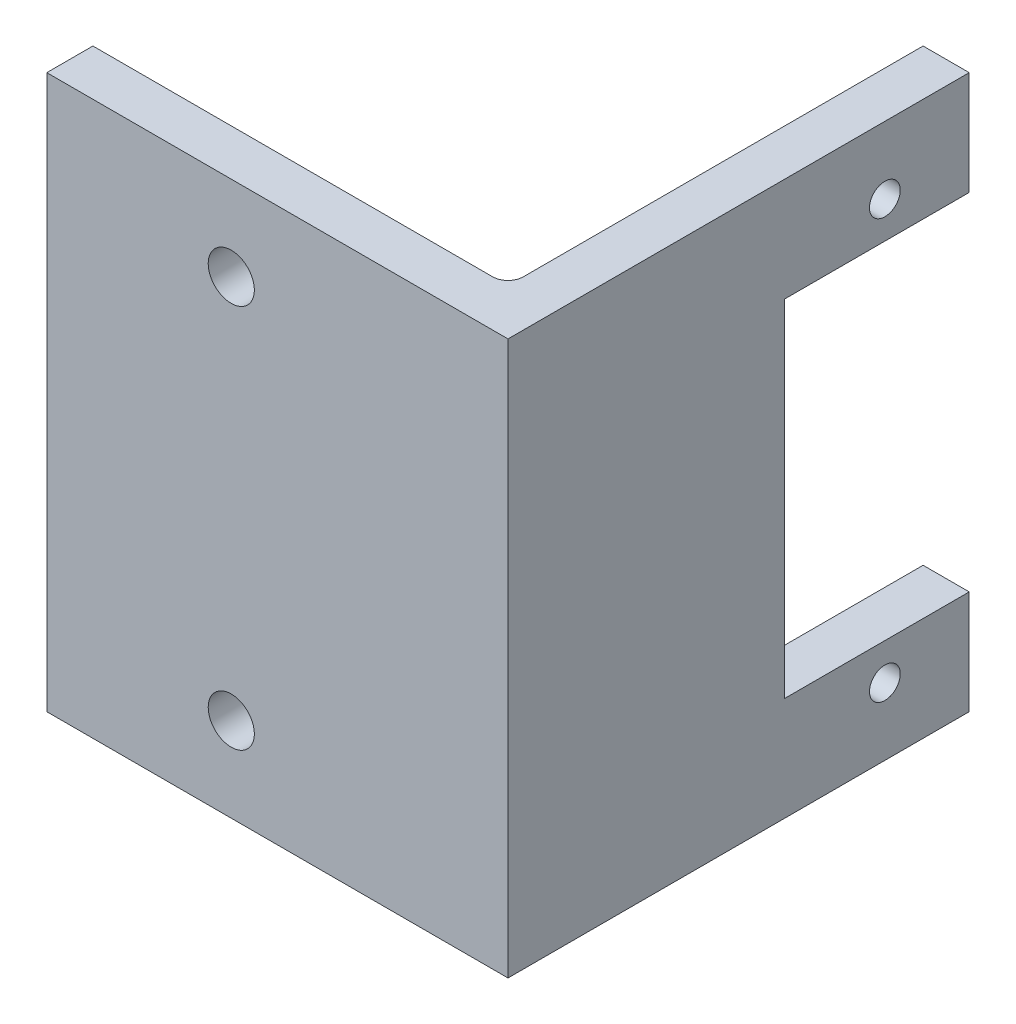
SolidWorks part; units mm, degrees
ref_plane "Front Plane" through (0, 0, 0) normal (0, 0, 1) x (1, 0, 0)
ref_plane "Top Plane" through (0, 0, 0) normal (0, 1, 0) x (1, 0, 0)
ref_plane "Right Plane" through (0, 0, 0) normal (1, 0, 0) x (0, 0, -1)
sketch "Sketch1" plane through (0, 0, 0) normal (0, 1, 0) x (1, 0, 0)
  line L0 (-15, 0) -> (15, 0)
  line L1 (15, 0) -> (15, 30)
  line L2 (0, 15.5838) -> (0, -19.0355) construction
  point P3 (0, 0)
  dimension "D1" = 30
  dimension "D2" = 30
extrude "Extrude-Thin1" add sketch "Sketch1" along normal mid plane 36 thin thin type one direction reverse wall 3
sketch "Sketch2" plane through (15, 0, 0) normal (1, 0, 0) x (0, 0, -1)
  line L0 (30, 18) -> (30, -18) construction
  line L1 (30, 11.25) -> (18, 11.25)
  line L2 (30, 11.25) -> (30, -11.25)
  line L3 (30, -11.25) -> (18, -11.25)
  line L4 (18, 11.25) -> (18, -11.25)
  line L7 (0, 0) -> (43.2029, 0) construction
  circle A0 centre (24.5132, 13.625) radius 1
  circle A1 centre (24.5132, -13.625) radius 1
  point P13 (0, 0)
  dimension "D3" = 2
  dimension "D1" = 22.5
  dimension "D2" = 12
  dimension "D4" = 27.25
extrude "Cut-Extrude1" cut sketch "Sketch2" against normal up to next
sketch "Sketch3" plane through (0, 0, -3) normal (0, 0, -1) x (-1, 0, 0)
  line L0 (15, 18) -> (15, -18) construction
  line L4 (0, 0) -> (20.4977, 0) construction
  circle A0 centre (3, 12.5) radius 1.5
  circle A1 centre (3, -12.5) radius 1.5
  point P7 (0, 0)
  dimension "D1" = 3
  dimension "D2" = 25
  dimension "D3" = 12
extrude "Cut-Extrude2" cut sketch "Sketch3" against normal up to next
sketch "Sketch4" plane through (12, 0, 0) normal (-1, 0, 0) x (0, 0, 1)
  line L0 (0, 0) -> (-26.6845, 0) construction
  line L1 (-18, 11.25) -> (-18, -11.25) construction
  line L2 (-18, -1.75) -> (0, -1.75)
  line L3 (-18, -1.75) -> (-18, 1.75)
  line L4 (-18, 1.75) -> (0, 1.75)
  line L5 (0, -1.75) -> (0, 1.75)
  line L6 (0, 18) -> (0, -18) construction
  dimension "D1" = 3.5
extrude "Boss-Extrude1" add sketch "Sketch4" along normal blind 20
sketch "Sketch5" plane through (0, 1.75, 0) normal (0, 1, 0) x (1, 0, 0)
  line L0 (-8, 3) -> (4.0773, 18)
  line L1 (-8, 18) -> (12, 18) construction
  line L2 (4.0773, 18) -> (-8, 18)
  line L3 (-8, 18) -> (-8, 3)
extrude "Cut-Extrude3" cut sketch "Sketch5" against normal up to next
fillet "Fillet1" radius 1 9 edges at (-1.9614, -1.75, -10.5) (-1.9614, 1.75, -10.5) (-8, 0, -3) (12, -1.75, -10.5) (2, -1.75, -3) (12, -9.875, -3) (12, 1.75, -10.5) (2, 1.75, -3) (12, 9.875, -3)
